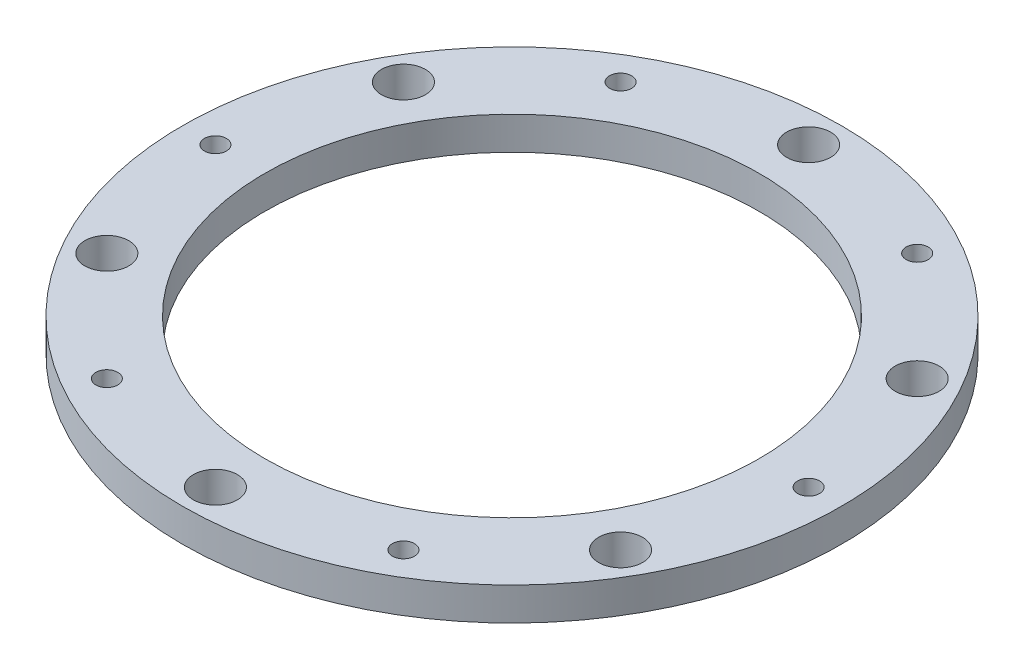
SolidWorks part; units mm, degrees
ref_plane "Front Plane" through (0, 0, 0) normal (0, 0, 1) x (1, 0, 0)
ref_plane "Top Plane" through (0, 0, 0) normal (0, 1, 0) x (1, 0, 0)
ref_plane "Right Plane" through (0, 0, 0) normal (1, 0, 0) x (0, 0, -1)
sketch "Sketch1" plane through (0, 0, 0) normal (0, 1, 0) x (1, 0, 0)
  circle A0 centre (0, 0) radius 30
  circle A1 centre (0, 0) radius 27 construction
  circle A2 centre (0, 27) radius 2
  circle A3 centre (23.3827, 13.5) radius 2
  circle A4 centre (23.3827, -13.5) radius 2
  circle A5 centre (0, -27) radius 2
  circle A6 centre (-23.3827, -13.5) radius 2
  circle A7 centre (-23.3827, 13.5) radius 2
  circle A8 centre (0, 0) radius 22.5
  point P18 (0, 0)
  dimension "D1" = 60
  dimension "D2" = 54
  dimension "D3" = 4
  dimension "D5" = 45
  dimension "D4" = 6
extrude "Boss-Extrude1" add sketch "Sketch1" along normal blind 3
sketch "Sketch3" plane through (0, 3, 0) normal (0, 1, 0) x (1, 0, 0)
  line L0 (-13.5, 23.3827) -> (0, 0) construction
  line L1 (0, 0) -> (12.944, 0) construction
  circle A0 centre (0, 0) radius 27 construction
  circle A1 centre (-13.5, 23.3827) radius 1
  circle A2 centre (13.5, 23.3827) radius 1
  circle A3 centre (27, 0) radius 1
  circle A4 centre (13.5, -23.3827) radius 1
  circle A5 centre (-13.5, -23.3827) radius 1
  circle A6 centre (-27, 0) radius 1
  point P17 (0, 0)
  dimension "D1" = 54
  dimension "D2" = 2
  dimension "D4" = 120
  dimension "D3" = 6
extrude "Cut-Extrude1" cut sketch "Sketch3" against normal blind 3
